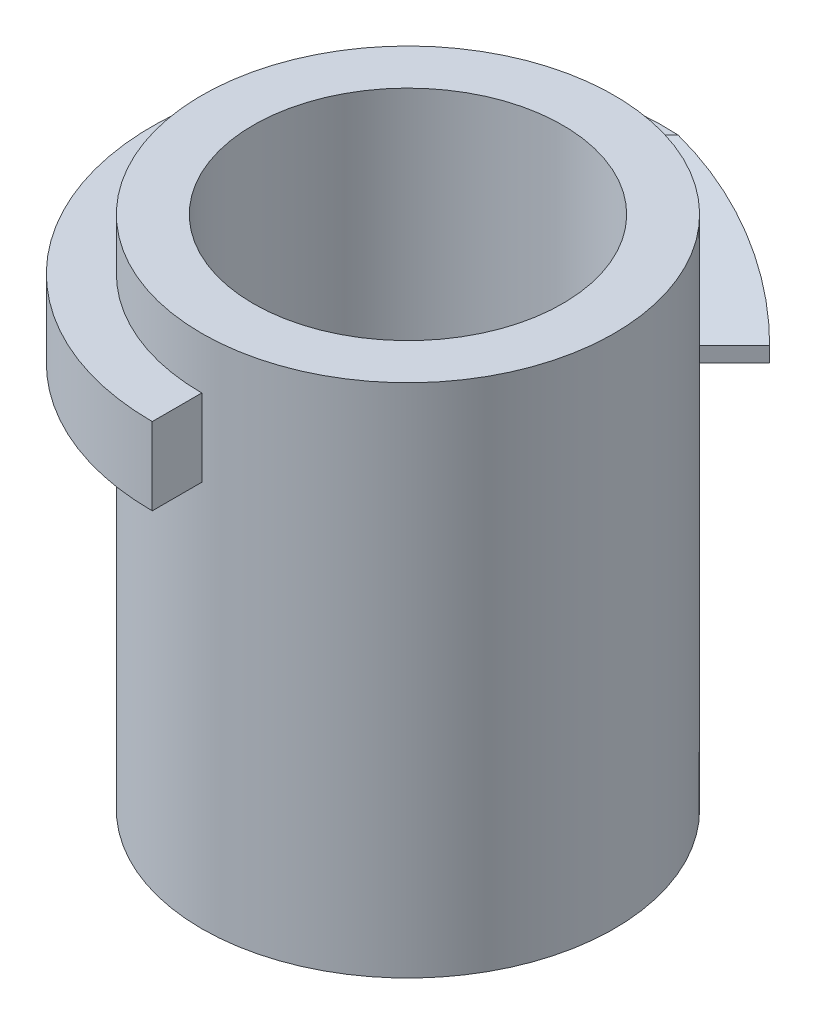
SolidWorks part; units mm, degrees
ref_plane "Front Plane" through (0, 0, 0) normal (0, 0, 1) x (1, 0, 0)
ref_plane "Top Plane" through (0, 0, 0) normal (0, 1, 0) x (1, 0, 0)
ref_plane "Right Plane" through (0, 0, 0) normal (1, 0, 0) x (0, 0, -1)
sketch "Sketch2" plane through (0, 0, 0) normal (0, 1, 0) x (1, 0, 0)
  circle A0 centre (0, 0) radius 10.16
extrude "Boss-Extrude1" add sketch "Sketch2" along normal blind 25.4
sketch "Sketch3" plane through (0, 25.4, 0) normal (0, 1, 0) x (1, 0, 0)
  circle A0 centre (0, 0) radius 7.62
extrude "Cut-Extrude1" cut sketch "Sketch3" against normal blind 20.32
sketch "Sketch4" plane through (0, 0, 0) normal (0, -1, 0) x (1, 0, 0)
  circle A0 centre (0, 0) radius 0.889
extrude "Cut-Extrude2" cut sketch "Sketch4" against normal blind 3.048
chamfer "Chamfer1" distance 0.381 angle 45 1 edges at (0, 0, -0.889)
chamfer "Chamfer2" distance 0.2159 angle 75 1 edges at (0, 3.048, -0.889) first distance on face at (0, 0.381, 0.889)
sketch "Sketch6" plane through (0, 25.4, 0) normal (0, 1, 0) x (1, 0, 0)
  circle A0 centre (0, 0) radius 12.5992
  circle A1 centre (0, 0) radius 10.16 construction
extrude "Boss-Extrude3" add sketch "Sketch6" against normal blind 6.35 contours A0
sketch "Sketch8" plane through (0, 25.4, 0) normal (0, 1, 0) x (1, 0, 0)
  circle A0 centre (0, 0) radius 7.62
extrude "Cut-Extrude4" cut sketch "Sketch8" against normal blind 12.7
sketch "Sketch9" plane through (0, 25.4, 0) normal (0, 1, 0) x (1, 0, 0)
  circle A1 centre (0, 0) radius 10.16
  circle A2 centre (0, 0) radius 12.5992
extrude "Cut-Extrude5" cut sketch "Sketch9" against normal blind 2.54
sketch "Sketch10" plane through (0, 22.86, 0) normal (0, 1, 0) x (1, 0, 0)
  line L0 (0, 0) -> (0, -12.5992)
  line L1 (0, 0) -> (8.909, 8.909)
  circle A0 centre (0, 0) radius 12.5992
  circle A1 centre (0, 0) radius 10.16
  circle M3 centre (0, 0) radius 10.16
  circle M4 centre (0, 0) radius 12.5992
extrude "Cut-Extrude7" cut sketch "Sketch10" against normal blind 4.826 contours L1 L0 M3 M4 region at (7.3605, 22.86, 7.3605)
chamfer "Chamfer3" distance 3.048 angle 70 1 edges at (8.0466, 22.86, -8.0466) first distance on face at (8.0466, 20.955, -8.0466)
equation "\".8n\"=1"
